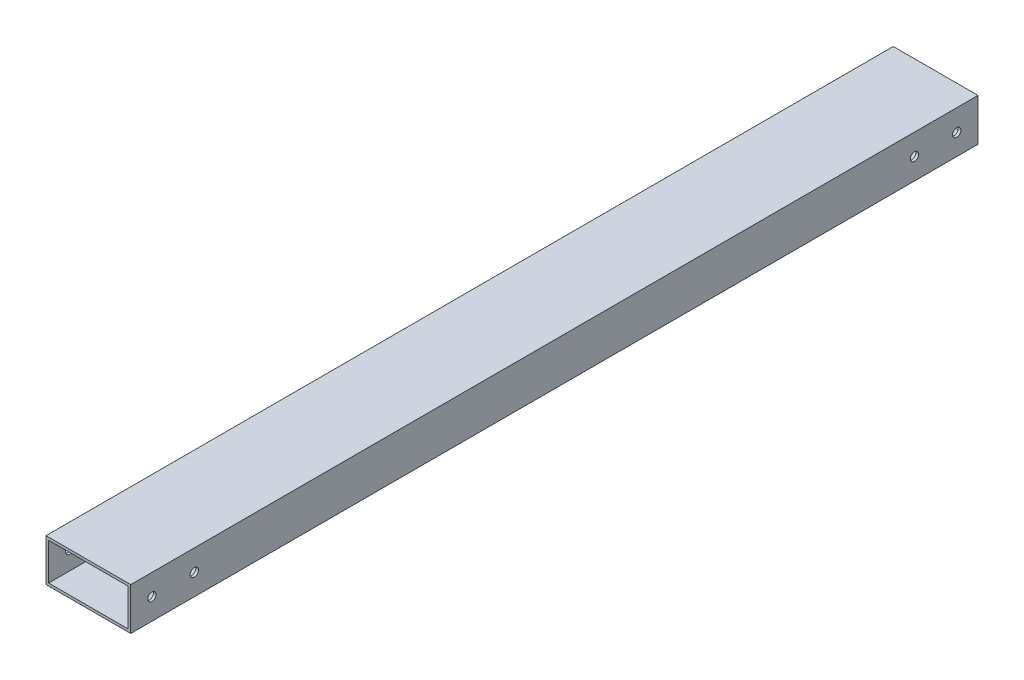
SolidWorks part; units mm, degrees
ref_plane "Front Plane" through (0, 0, 0) normal (0, 0, 1) x (1, 0, 0)
ref_plane "Top Plane" through (0, 0, 0) normal (0, 1, 0) x (1, 0, 0)
ref_plane "Right Plane" through (0, 0, 0) normal (1, 0, 0) x (0, 0, -1)
sketch "Sketch1" plane through (0, 0, 0) normal (0, 0, 1) x (1, 0, 0)
  line L0 (-23.8125, 11.1125) -> (23.8125, 11.1125)
  line L2 (-25.4, 12.7) -> (25.4, 12.7)
  line L3 (-25.4, 12.7) -> (-25.4, -12.7)
  line L4 (-25.4, -12.7) -> (25.4, -12.7)
  line L5 (25.4, 12.7) -> (25.4, -12.7)
  line L10 (23.8125, 11.1125) -> (23.8125, -11.1125)
  line L11 (-23.8125, -11.1125) -> (23.8125, -11.1125)
  line L12 (-23.8125, 11.1125) -> (-23.8125, -11.1125)
  point P12 (0, 12.7)
  point P14 (25.4, 0)
  dimension "Wall Thickness" = 1.5875
  dimension "Outside Width" = 50.8
  dimension "Outside Height" = 25.4
  dimension "Inside Height" = 22.225
  dimension "Inside Width" = 47.625
sketch "Sketch2" plane through (0, 0, 0) normal (1, 0, 0) x (0, 0, -1)
  line L0 (254, 0) -> (-254, 0)
  point P4 (0, 0)
  point P7 (-254, 0)
  point P10 (254, 0)
  dimension "Length" = 508
sketch "Sketch3" plane through (0, 0, 0) normal (0, 0, 1) x (1, 0, 0)
  line L21 (25.4, 12.7) -> (-25.4, 12.7)
  line L22 (25.4, -12.7) -> (25.4, 12.7)
  line L23 (-25.4, -12.7) -> (25.4, -12.7)
  line L24 (-25.4, 12.7) -> (-25.4, -12.7)
  line L25 (25.4, 12.7) -> (-25.4, 12.7)
  line L26 (25.4, -12.7) -> (25.4, 12.7)
  line L27 (-25.4, -12.7) -> (25.4, -12.7)
  line L28 (-25.4, 12.7) -> (-25.4, -12.7)
  line L29 (23.8125, 11.1125) -> (-23.8125, 11.1125)
  line L30 (23.8125, -11.1125) -> (23.8125, 11.1125)
  line L31 (-23.8125, -11.1125) -> (23.8125, -11.1125)
  line L32 (-23.8125, 11.1125) -> (-23.8125, -11.1125)
  line L33 (23.8125, 11.1125) -> (-23.8125, 11.1125)
  line L34 (23.8125, -11.1125) -> (23.8125, 11.1125)
  line L35 (-23.8125, -11.1125) -> (23.8125, -11.1125)
  line L36 (-23.8125, 11.1125) -> (-23.8125, -11.1125)
  dimension "D1" = 0
  dimension "D2" = 0
extrude "Boss-Extrude1" add sketch "Sketch3" along normal up to vertex (254 mm away) and the other way up to vertex (254 mm away) up to point (0, 0, 254) other way up to point (0, 0, -254)
sketch "Drawing Reference" plane through (0, 0, 0) normal (1, 0, 0) x (0, 0, -1)
  line L0 (-254, 0) -> (254, 0) construction
  line L1 (0, -12.7) -> (0, 12.7) construction
  line L2 (-254, -12.7) -> (254, -12.7) construction
  line L5 (-254, 12.7) -> (254, 12.7) construction
  point P7 (-217.424, 0)
  point P8 (217.424, 0)
  dimension "D1" = 36.576
hole_wizard "#10 Clearance Hole1" positions "Sketch4" profile "Sketch5" hole size "#10" standard "ANSI Inch" end condition through all
sketch "Sketch4" plane through (25.4, 0, 0) normal (1, 0, 0) x (0, 0, -1)
  point P3 (-215.9, 0)
  point P12 (-241.3, 0)
  point P18 (215.9, 0)
  point P23 (241.2618, -0.1635)
sketch "Sketch5" plane through (25.4, 0, 215.9) normal (0, 1, 0) x (0, 0, -1)
  line L0 (0, 0) -> (0, 50.8)
  line L1 (0, 50.8) -> (2.4892, 50.8)
  line L2 (2.4892, 50.8) -> (2.4892, 0)
  line L5 (2.4892, 0) -> (0, 0)
  line L11 (0, -6.35) -> (0, 107.95) construction
  dimension "Thru Hole Dia." = 4.9784
  dimension "Thru Hole Depth" = 50.8
equation "\"D1@Drawing Reference\"=\"Outside Width@Sketch1\" * 0.72"
